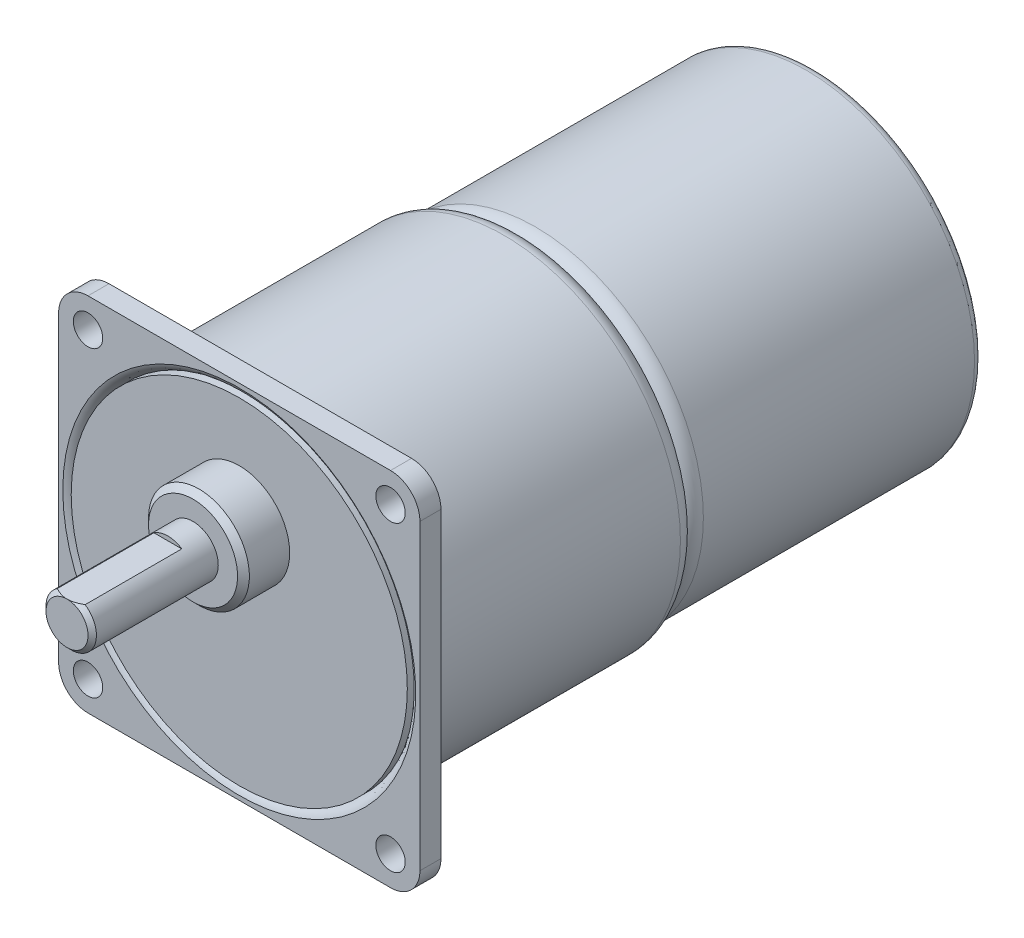
SolidWorks part; units mm, degrees
ref_plane "Front Plane" through (0, 0, 0) normal (0, 0, 1) x (1, 0, 0)
ref_plane "Top Plane" through (0, 0, 0) normal (0, 1, 0) x (1, 0, 0)
ref_plane "Right Plane" through (0, 0, 0) normal (1, 0, 0) x (0, 0, -1)
sketch "Sketch1" plane through (0, 0, 0) normal (0, 0, 1) x (1, 0, 0)
  line L0 (3.5, -3.5) -> (39.5, -3.5) construction
  line L1 (3.5, 0) -> (39.5, 0)
  line L2 (0, -3.5) -> (0, -39.5)
  line L3 (3.5, -43) -> (39.5, -43)
  line L4 (43, -3.5) -> (43, -39.5)
  line L5 (39.5, -3.5) -> (39.5, -39.5) construction
  line L6 (39.5, -39.5) -> (3.5, -39.5) construction
  line L7 (3.5, -39.5) -> (3.5, -3.5) construction
  line L8 (0, -21.5) -> (43, -21.5) construction
  line L9 (21.5, 0) -> (21.5, -43) construction
  circle A0 centre (3.5, -3.5) radius 1.75
  circle A1 centre (39.5, -3.5) radius 1.75
  circle A2 centre (3.5, -39.5) radius 1.75
  circle A3 centre (39.5, -39.5) radius 1.75
  arc A4 (3.5, 0) -> (0, -3.5) centre (3.5, -3.5) ccw
  arc A5 (39.5, 0) -> (43, -3.5) centre (39.5, -3.5) cw
  arc A6 (39.5, -43) -> (43, -39.5) centre (39.5, -39.5) ccw
  arc A7 (0, -39.5) -> (3.5, -43) centre (3.5, -39.5) ccw
  point P13 (21.5, -3.5)
  point P14 (3.5, -21.5)
  point P21 (0, 0)
  point P24 (43, 0)
  point P29 (0, -43)
  dimension "D5" = 3.5
  dimension "D6" = 3.5
  dimension "D1" = 43
  dimension "D2" = 43
  dimension "D3" = 36
  dimension "D4" = 36
extrude "Boss-Extrude1" add sketch "Sketch1" along normal blind 2.5
sketch "Sketch2" plane through (0, 0, 2.5) normal (0, 0, 1) x (1, 0, 0)
  line L0 (21.5, 0) -> (21.5, -43) construction
  line L1 (39.5, 0) -> (3.5, 0) construction
  line L2 (3.5, -43) -> (39.5, -43) construction
  line L3 (43, -21.5) -> (0, -21.5) construction
  line L4 (43, -39.5) -> (43, -3.5) construction
  line L5 (0, -3.5) -> (0, -39.5) construction
  circle A0 centre (21.5, -14.5) radius 6
  dimension "D2" = 12
  dimension "D1" = 7
extrude "Boss-Extrude2" add sketch "Sketch2" along normal blind 5.5
sketch "Sketch3" plane through (0, 0, 8) normal (0, 0, 1) x (1, 0, 0)
  circle A0 centre (21.5, -14.5) radius 3
  dimension "D1" = 6
extrude "Boss-Extrude3" add sketch "Sketch3" along normal blind 15
chamfer "Chamfer1" distance 0.7 angle 45 1 edges at (27.5, -14.5, 8)
sketch "Sketch4" plane through (43, 0, 0) normal (1, 0, 0) x (0, 0, -1)
  line L0 (-23, -17.5) -> (-8, -17.5) construction
  line L1 (-11, -9.2) -> (-23, -9.2)
  line L2 (-11, -9.2) -> (-11, -12)
  line L3 (-11, -12) -> (-23, -12)
  line L4 (-23, -9.2) -> (-23, -12)
  line L5 (-23, -11.5) -> (-23, -17.5) construction
  dimension "D1" = 5.5
  dimension "D2" = 12
extrude "Cut-Extrude1" cut sketch "Sketch4" against normal through all
chamfer "Chamfer2" distance 0.5 angle 45 1 edges at (21.5, -17.5, 23)
sketch "Sketch5" plane through (0, 0, 0) normal (0, 0, -1) x (-1, 0, 0)
  line L0 (-21.5, 0) -> (-21.5, -43) construction
  line L1 (-39.5, 0) -> (-3.5, 0) construction
  line L2 (-3.5, -43) -> (-39.5, -43) construction
  line L3 (0, -21.5) -> (-43, -21.5) construction
  line L4 (0, -3.5) -> (0, -39.5) construction
  line L5 (-43, -39.5) -> (-43, -3.5) construction
  circle A0 centre (-21.5, -21.5) radius 21
  dimension "D1" = 42
extrude "Boss-Extrude4" add sketch "Sketch5" along normal blind 31
fillet "Fillet1" radius 2 1 edges at (0.5, -21.5, -31)
sketch "Sketch6" plane through (0, 0, -31) normal (0, 0, -1) x (-1, 0, 0)
  circle A0 centre (-21.5, -21.5) radius 20
  dimension "D1" = 40
extrude "Boss-Extrude5" add sketch "Sketch6" along normal blind 35
fillet "Fillet2" radius 2 1 edges at (1.5, -21.5, -31)
fillet "Fillet3" radius 1 1 edges at (1.5, -21.5, -66)
ref_plane "Plane1" through (21.5, 0, 0) normal (1, 0, 0) x (0, 0, -1)
sketch "Sketch7" plane through (21.5, 0, 0) normal (1, 0, 0) x (0, 0, -1)
  line L0 (66, -21.5) -> (-10.9591, -21.5) construction
  line L1 (66, -40.5) -> (66, -2.5) construction
  line L2 (-2.5, -43) -> (-2.5, 0) construction
  line L3 (-2.5, -1.5) -> (-1.5, -1.5)
  line L4 (-2.5, -1.5) -> (-2.5, -0.5) construction
  line L5 (-2.5, -0.5) -> (-2.5, -1.5)
  spline S0 degree 2 poles (-2.5, -0.5) (-2.2, -1.2) (-1.5, -1.5) knots 0 0 0 1 1 1
  dimension "D1" = 1
  dimension "D2" = 1
  dimension "D3" = 0.4
  dimension "D4" = 0.4
  dimension "D5" = 20
revolve "Cut-Revolve1" cut sketch "Sketch7" angle 360 about L0
